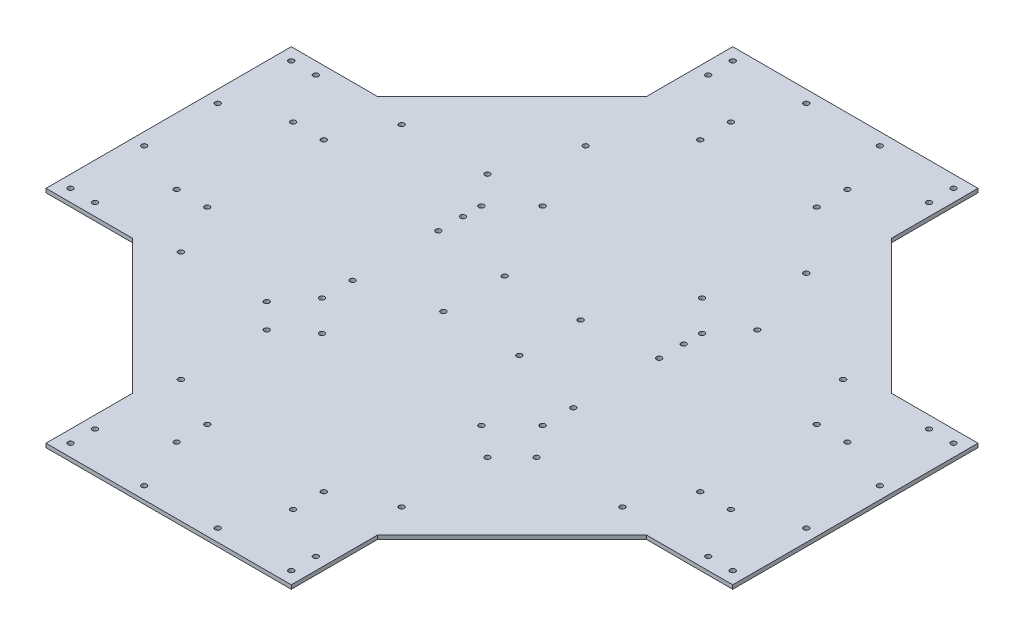
SolidWorks part; units mm, degrees
ref_plane "Front Plane" through (0, 0, 0) normal (0, 0, 1) x (1, 0, 0)
ref_plane "Top Plane" through (0, 0, 0) normal (0, 1, 0) x (1, 0, 0)
ref_plane "Right Plane" through (0, 0, 0) normal (1, 0, 0) x (0, 0, -1)
sketch "Sketch1" plane through (0, 0, 0) normal (0, 1, 0) x (1, 0, 0)
  line L0 (0, -280) -> (100, -280)
  line L1 (100, -280) -> (100, -209.6016)
  line L2 (280, -100) -> (209.6016, -100)
  line L3 (0, 0) -> (0, -280) construction
  line L4 (280, 0) -> (280, -100)
  line L5 (-280, 280) -> (280, 280) construction
  line L6 (-280, 280) -> (-280, -280) construction
  line L7 (-280, -280) -> (280, -280) construction
  line L8 (280, 280) -> (280, -280) construction
  line L9 (-280, 280) -> (280, -280) construction
  line L10 (-280, -280) -> (280, 280) construction
  line L11 (100, -209.6016) -> (209.6016, -100)
  line L12 (-280, 0) -> (-280, -100)
  line L13 (-280, -100) -> (-209.6016, -100)
  line L14 (-209.6016, -100) -> (-100, -209.6016)
  line L15 (-100, -280) -> (-100, -209.6016)
  line L16 (0, -280) -> (-100, -280)
  line L17 (0, 280) -> (-100, 280)
  line L18 (-100, 280) -> (-100, 209.6016)
  line L19 (-100, 209.6016) -> (-209.6016, 100)
  line L20 (-280, 100) -> (-209.6016, 100)
  line L21 (-280, 0) -> (-280, 100)
  line L22 (280, 0) -> (280, 100)
  line L23 (280, 100) -> (209.6016, 100)
  line L24 (209.6016, 100) -> (100, 209.6016)
  line L25 (100, 280) -> (100, 209.6016)
  line L26 (0, 280) -> (100, 280)
  line L27 (111.5258, -219.2889) -> (219.2889, -111.5258) construction
  line L28 (219.2889, -111.5258) -> (247.5732, -139.8101) construction
  line L29 (247.5732, -139.8101) -> (139.8101, -247.5732) construction
  line L30 (139.8101, -247.5732) -> (111.5258, -219.2889) construction
  line L31 (-100, -270) -> (100, -270) construction
  line L32 (-90, -280) -> (-90, 280) construction
  line L33 (-75, -75) -> (75, -75) construction
  line L34 (-75, -75) -> (-75, 75) construction
  line L35 (-75, 75) -> (75, 75) construction
  line L36 (75, -75) -> (75, 75) construction
  line L37 (-75, -75) -> (75, 75) construction
  line L38 (-75, 75) -> (75, -75) construction
  line L39 (-100, -260) -> (100, -260) construction
  line L40 (-280, 40) -> (280, 40) construction
  line L41 (0, 280) -> (0, 0) construction
  line L42 (-280, -90) -> (280, -90) construction
  line L43 (-260, -100) -> (-260, 100) construction
  line L44 (0, 0) -> (-280, 0) construction
  arc A0 (100, -280) -> (280, -100) centre (100, -100) ccw construction
  circle A1 centre (-47.5, -201) radius 2.125
  circle A2 centre (-47.5, -226) radius 2.125
  circle A3 centre (47.5, -226) radius 2.125
  circle A4 centre (47.5, -201) radius 2.125
  circle A5 centre (-201, 47.5) radius 2.125
  circle A6 centre (-226, 47.5) radius 2.125
  circle A7 centre (-201, -47.5) radius 2.125
  circle A8 centre (-226, -47.5) radius 2.125
  circle A9 centre (47.5, 201) radius 2.125
  circle A10 centre (47.5, 226) radius 2.125
  circle A11 centre (-47.5, 201) radius 2.125
  circle A12 centre (-47.5, 226) radius 2.125
  circle A13 centre (201, -47.5) radius 2.125
  circle A14 centre (226, -47.5) radius 2.125
  circle A15 centre (201, 47.5) radius 2.125
  circle A16 centre (226, 47.5) radius 2.125
  circle A17 centre (-90, -270) radius 2.125
  circle A18 centre (-30, -270) radius 2.125
  circle A19 centre (30, -270) radius 2.125
  circle A20 centre (90, -270) radius 2.125
  circle A21 centre (-270, 90) radius 2.125
  circle A22 centre (-270, 30) radius 2.125
  circle A23 centre (-270, -30) radius 2.125
  circle A24 centre (-270, -90) radius 2.125
  circle A25 centre (90, 270) radius 2.125
  circle A26 centre (30, 270) radius 2.125
  circle A27 centre (-30, 270) radius 2.125
  circle A28 centre (-90, 270) radius 2.125
  circle A29 centre (270, -90) radius 2.125
  circle A30 centre (270, -30) radius 2.125
  circle A31 centre (270, 30) radius 2.125
  circle A32 centre (270, 90) radius 2.125
  circle A33 centre (-90, -250) radius 2.125
  circle A34 centre (-90, -180) radius 2.125
  circle A35 centre (-90, -110) radius 2.125
  circle A36 centre (-90, -40) radius 2.125
  circle A37 centre (-90, 30) radius 2.125
  circle A38 centre (-90, 50) radius 2.125
  circle A39 centre (-90, 100) radius 2.125 construction
  circle A40 centre (-90, 150) radius 2.125
  circle A41 centre (-90, 200) radius 2.125 construction
  circle A42 centre (-90, 250) radius 2.125
  circle A43 centre (90, -250) radius 2.125
  circle A44 centre (90, -180) radius 2.125
  circle A45 centre (90, -110) radius 2.125
  circle A46 centre (90, -40) radius 2.125
  circle A47 centre (90, 30) radius 2.125
  circle A48 centre (90, 50) radius 2.125
  circle A49 centre (90, 100) radius 2.125 construction
  circle A50 centre (90, 150) radius 2.125
  circle A51 centre (90, 200) radius 2.125 construction
  circle A52 centre (90, 250) radius 2.125
  circle A53 centre (-250, -90) radius 2.125
  circle A54 centre (-180, -90) radius 2.125
  circle A55 centre (-110, -90) radius 2.125
  circle A56 centre (-110, 90) radius 2.125
  circle A57 centre (-180, 90) radius 2.125
  circle A58 centre (-250, 90) radius 2.125
  circle A59 centre (110, -90) radius 2.125
  circle A60 centre (180, -90) radius 2.125
  circle A61 centre (250, -90) radius 2.125
  circle A62 centre (110, 90) radius 2.125
  circle A63 centre (180, 90) radius 2.125
  circle A64 centre (250, 90) radius 2.125
  point P33 (0, 0)
  point P68 (0, 0)
  point P107 (0, 0)
  dimension "D10" = 25
  dimension "4.25" = 4.25
  dimension "D11" = 4.25
  dimension "D16" = 4.25
  dimension "D24" = 4.25
  dimension "D28" = 4.25
  dimension "D32" = 4.25
  dimension "D1" = 560
  dimension "D2" = 90
  dimension "D3" = 280
  dimension "D4" = 4
  dimension "D5" = 100
  dimension "D6" = 155
  dimension "D7" = 152.4
  dimension "D8" = 15
  dimension "D9" = 40
  dimension "D12" = 47.5
  dimension "D13" = 54
  dimension "D15" = 10
  dimension "D17" = 10
  dimension "D18" = 76.2
  dimension "D19" = 150
  dimension "D20" = 150
  dimension "D23" = 10
  dimension "D25" = 10
  dimension "D26" = 300
  dimension "D29" = 10
  dimension "D31" = 20
  dimension "D33" = 10
  dimension "D21" = 4
  dimension "D27" = 5
  dimension "D30" = 5
  dimension "D34" = 3
  dimension "D14" = 4
  dimension "D22" = 4
extrude "Boss-Extrude1" add sketch "Sketch1" along normal blind 3.175 contours L26 L17 L18 L19 L20 L21 L12 L13 L14 L15 L16 L0 L1 L11 L2 L4 L22 L23 L24 L25 region at (0, 0, -0.0137)
sketch "Sketch2" plane through (0, 3.175, 0) normal (0, 1, 0) x (1, 0, 0)
  line L0 (0, 25.5202) -> (0, -25) construction
  line L1 (-31, -25) -> (31, -25) construction
  line L2 (-31, -25) -> (-31, 25) construction
  line L3 (-31, 25) -> (31, 25) construction
  line L4 (31, -25) -> (31, 25) construction
  line L5 (-31, -25) -> (31, 25) construction
  line L6 (-31, 25) -> (31, -25) construction
  line L7 (75, -75) -> (75, 75) construction
  line L8 (-75, -75) -> (75, -75) construction
  line L9 (-75, -75) -> (-75, 75) construction
  line L10 (-75, 75) -> (75, 75) construction
  line L11 (75, -75) -> (75, 75) construction
  line L12 (-75, -75) -> (75, -75) construction
  line L13 (-75, -75) -> (-75, 75) construction
  line L14 (-75, 75) -> (75, 75) construction
  line L15 (-90, 270) -> (-90, -270) construction
  line L16 (-270, 90) -> (270, 90) construction
  circle A0 centre (-31, 25) radius 2.125
  circle A1 centre (-31, -25) radius 2.125
  circle A2 centre (31, -25) radius 2.125
  circle A3 centre (31, 25) radius 2.125
  circle A4 centre (-90, 65) radius 2.125
  circle A5 centre (-65, 90) radius 2.125
  circle A6 centre (65, 90) radius 2.125
  circle A7 centre (90, 65) radius 2.125
  circle A8 centre (90, -65) radius 2.125
  circle A9 centre (65, -90) radius 2.125
  circle A10 centre (-65, -90) radius 2.125
  circle A11 centre (-90, -65) radius 2.125
  point P0 (0, 0)
  point P43 (0, 0)
  dimension "D3" = 4.25
  dimension "D4" = 4.25
  dimension "D5" = 4.25
  dimension "D7" = 4.25
  dimension "D1" = 62
  dimension "D2" = 50
  dimension "D6" = 10
  dimension "D8" = 10
  dimension "D9" = 4
extrude "Cut-Extrude1" cut sketch "Sketch2" against normal through all
